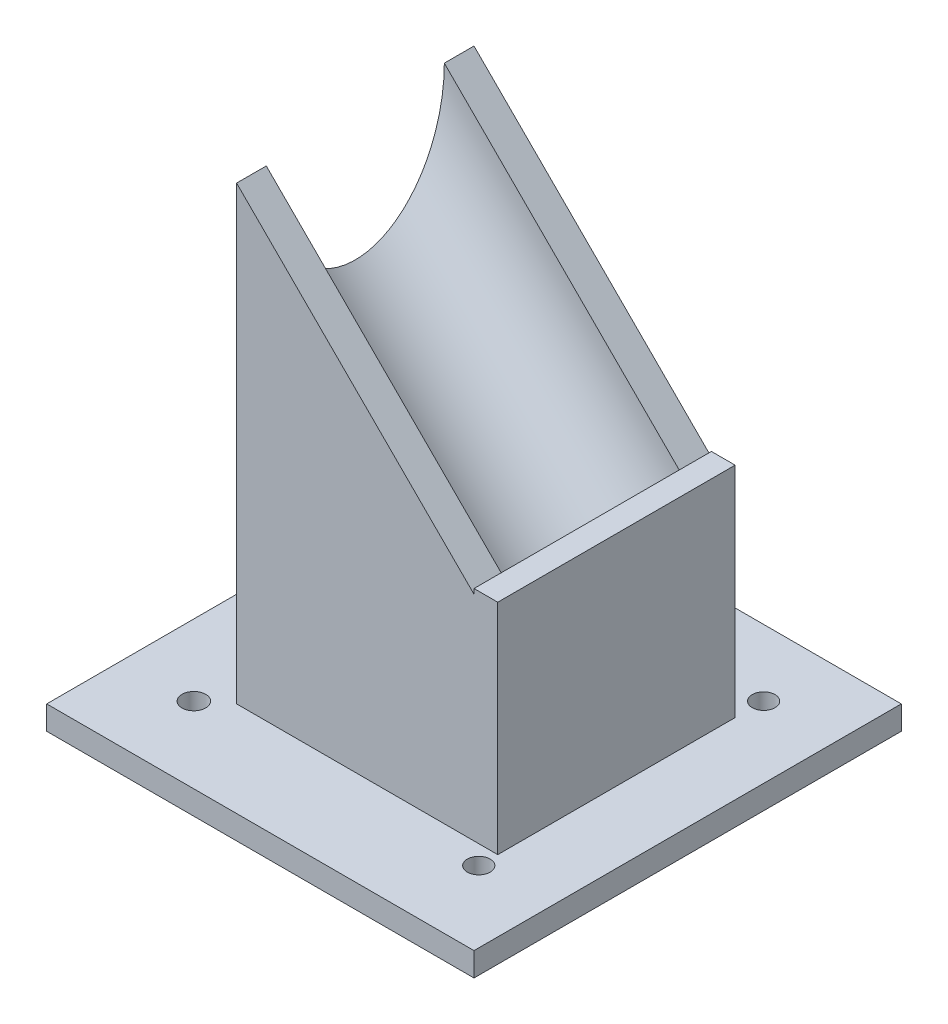
SolidWorks part; units mm, degrees
ref_plane "Front Plane" through (0, 0, 0) normal (0, 0, 1) x (1, 0, 0)
ref_plane "Top Plane" through (0, 0, 0) normal (0, 1, 0) x (1, 0, 0)
ref_plane "Right Plane" through (0, 0, 0) normal (1, 0, 0) x (0, 0, -1)
sketch "Sketch1" plane through (0, 0, 0) normal (0, 0, 1) x (1, 0, 0)
  line L1 (0, 0) -> (-50, 0)
  line L2 (0, 0) -> (0, 50)
  line L3 (0, 50) -> (-50, 50)
  line L4 (-50, 0) -> (-50, 50)
  dimension "D1" = 50
  dimension "D2" = 50
extrude "Boss-Extrude1" add sketch "Sketch1" along normal blind 50
sketch "Sketch2" plane through (0, 0, 50) normal (0, 0, 1) x (1, 0, 0)
  line L4 (0, 50) -> (-50, 50)
  line L5 (-50, 50) -> (-50, 100)
  line L6 (-50, 100) -> (0, 50)
extrude "Boss-Extrude2" add sketch "Sketch2" against normal blind 50
sketch "Sketch4" plane through (25, 25, 0) normal (0.7071, 0.7071, 0) x (0, 0, -1)
  line L0 (-25, 106.066) -> (-25, 35.3553) construction
  line L1 (0, 106.066) -> (-50, 106.066) construction
  line L2 (-50, 35.3553) -> (0, 35.3553) construction
  line L3 (-25, 35.3553) -> (-43.75, 35.3553)
  line L4 (-43.75, 35.3553) -> (-43.75, 106.066)
  line L5 (-43.75, 106.066) -> (-25, 106.066)
  line L6 (-25, 106.066) -> (-25, 35.3553)
revolve "Revolve1" add sketch "Sketch4" angle 360 about L6
sketch "Sketch5" plane through (-25, 25, 0) normal (0.7071, -0.7071, 0) x (0, 0, -1)
  line L0 (-43.75, 35.3553) -> (-6.25, 35.3553) construction
  circle A0 centre (-25, 35.3553) radius 18.75
extrude "Cut-Extrude2" cut sketch "Sketch5" against normal blind 100 and the other way blind 100
sketch "Sketch6" plane through (0, 0, 0) normal (0, -1, 0) x (1, 0, 0)
  line L0 (-50, 50) -> (0, 50) construction
  line L2 (-50, 50) -> (-50, 0)
  line L3 (-50, -20) -> (20, -20)
  line L4 (20, 50) -> (20, -20)
  line L5 (-50, 50) -> (-50, 0) construction
  line L6 (0, 70) -> (20, 70)
  line L9 (0, 70) -> (-70, 70)
  line L10 (-70, 0) -> (-70, 70)
  line L11 (20, 70) -> (20, 50)
  line L12 (-70, 0) -> (-70, -20)
  line L13 (-70, -20) -> (-50, -20)
  line M7 (-50, 0) -> (0, 0)
  line M8 (0, 0) -> (0, 50)
  line M9 (0, 50) -> (-50, 50)
  line M10 (-50, 50) -> (-50, 0)
  dimension "D1" = 70
  dimension "D2" = 70
  dimension "D3" = 70
  dimension "D4" = 70
extrude "Boss-Extrude3" add sketch "Sketch6" against normal blind 5 contours L12 L13 L3 L4 L11 L6 L9 L10 M7 M10 M9 M8 region at (-60, 0, -18.7272)
sketch "Sketch7" plane through (25, 25, 0) normal (0.7071, 0.7071, 0) x (0, 0, -1)
  line L0 (-43.75, 35.3553) -> (-25, 35.3553)
  line L1 (-25, 35.3553) -> (-25, 106.066)
  line L2 (-25, 106.066) -> (-43.75, 106.066)
  line L3 (-43.75, 106.066) -> (-43.75, 35.3553)
revolve "Revolve2" add sketch "Sketch7" angle 360 about L1
sketch "Sketch9" plane through (-25, 25, 0) normal (0.7071, -0.7071, 0) x (0, 0, -1)
  circle A0 centre (-25.1097, 35.312) radius 18.8679
extrude "Boss-Extrude6" add sketch "Sketch9" along normal blind 20
sketch "Sketch10" plane through (0, 0, 0) normal (1, 0, 0) x (0, 0, -1)
  line L0 (-50, 5) -> (-50, 50) construction
  line L1 (-50, 16.5448) -> (0, 16.5448)
  line L2 (-50, 16.5448) -> (-50, 81.6917)
  line L3 (-50, 81.6917) -> (0, 81.6917)
  line L4 (0, 16.5448) -> (0, 81.6917)
  line L5 (0, 50) -> (0, 100) construction
extrude "Cut-Extrude3" cut sketch "Sketch10" along normal blind 40
sketch "Sketch11" plane through (-75, 75, 0) normal (-0.7071, 0.7071, 0) x (0, 0, 1)
  circle A0 centre (25, 35.3553) radius 18.75
extrude "Cut-Extrude4" cut sketch "Sketch11" against normal blind 70
sketch "Sketch12" plane through (0, 0, 0) normal (1, 0, 0) x (0, 0, -1)
  line L0 (0, 50) -> (0, 100) construction
  line L1 (-50, 5) -> (0, 5)
  line L2 (-50, 5) -> (-50, 51.0471)
  line L3 (-50, 51.0471) -> (0, 51.0471)
  line L4 (0, 5) -> (0, 51.0471)
extrude "Boss-Extrude7" add sketch "Sketch12" along normal blind 5
sketch "Sketch13" plane through (0, 5, 0) normal (0, 1, 0) x (1, 0, 0)
  line L0 (-70, 20) -> (20, 20) construction
  line L1 (-55, -54) -> (5, -54) construction
  line L2 (-55, -54) -> (-55, 6) construction
  line L3 (-55, 6) -> (5, 6) construction
  line L4 (5, -54) -> (5, 6) construction
  line L5 (-70, -70) -> (-70, 20) construction
  circle A0 centre (5, 6) radius 2.4
  circle A1 centre (5, -54) radius 2.4
  circle A2 centre (-55, 6) radius 2.5
  circle A3 centre (-55, -54) radius 2.5
  dimension "D1" = 60
  dimension "D2" = 60
  dimension "D3" = 14
  dimension "D4" = 15
extrude "Cut-Extrude5" cut sketch "Sketch13" against normal blind 5
